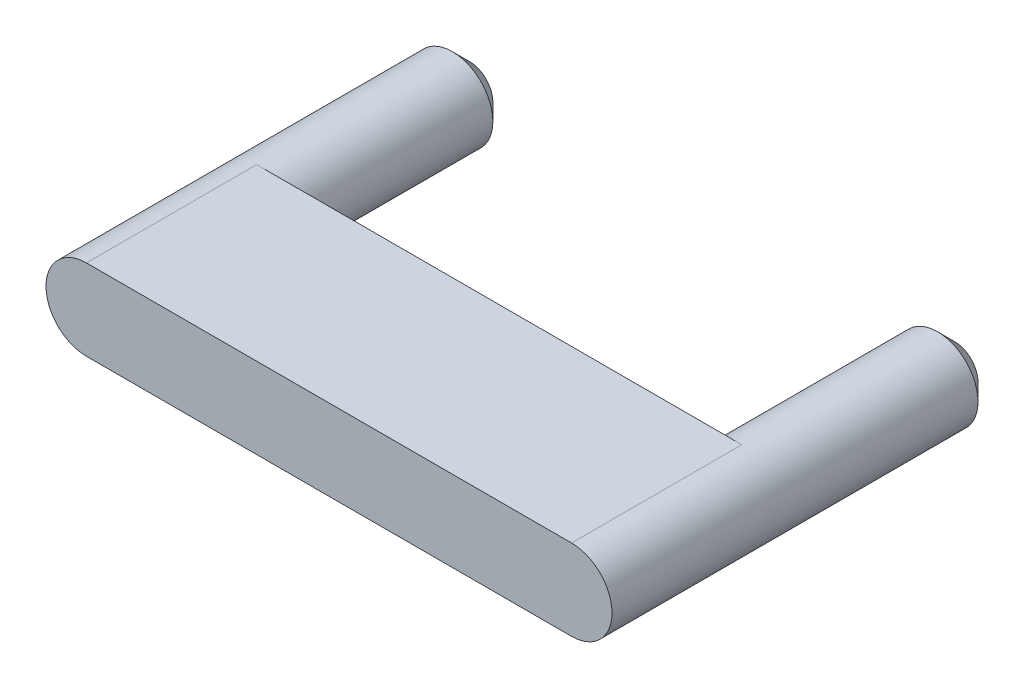
SolidWorks part; units mm, degrees
note: The reader was unsure of these and kept them because the rebuilt part matched: shared geometry of "Sketch1<4>".
ref_plane "Front Plane" through (0, 0, 0) normal (0, 0, 1) x (1, 0, 0)
ref_plane "Top Plane" through (0, 0, 0) normal (0, 1, 0) x (1, 0, 0)
ref_plane "Right Plane" through (0, 0, 0) normal (1, 0, 0) x (0, 0, -1)
sketch "Sketch1" plane through (0, 0, 0) normal (0, 0, 1) x (1, 0, 0)
  line L5 (11.4, 0.95) -> (0, 0.95)
  line L6 (11.4, 0.95) -> (11.4, -0.95)
  line L7 (11.4, -0.95) -> (0, -0.95)
  line L8 (0, 0.95) -> (0, -0.95)
  circle A0 centre (0, 0) radius 0.95
  circle A1 centre (11.4, 0) radius 0.95
  circle A2 centre (0, -47) radius 0.95
  circle A3 centre (11.4, -47) radius 0.95
  dimension "D3" = 1.9
  dimension "D1" = 11.4
  dimension "D2" = 47
extrude "Boss-Extrude1" add sketch "Sketch1" along normal blind 4
extrude "Boss-Extrude2" add sketch "Sketch1<4>" against normal blind 5 contours A0 | A1
sketch "Sketch1<4>" plane through (0, 0, 0) normal (0, 0, 1) x (1, 0, 0) same geometry as "Sketch1"
chamfer "Chamfer1" distance 0.4 angle 45 2 edges at (0.95, 0, -5) (12.35, 0, -5)
sketch "Sketch2" plane through (0, 0, 4) normal (0, 0, 1) x (1, 0, 0)
  line L0 (0, -1.95) -> (11.4, -1.95)
  line L1 (0, 1.95) -> (11.4, 1.95)
  circle A0 centre (0, 0) radius 1.95
  circle A1 centre (11.4, 0) radius 1.95
  circle A2 centre (0, 0) radius 0.95 construction
  dimension "D1" = 1
